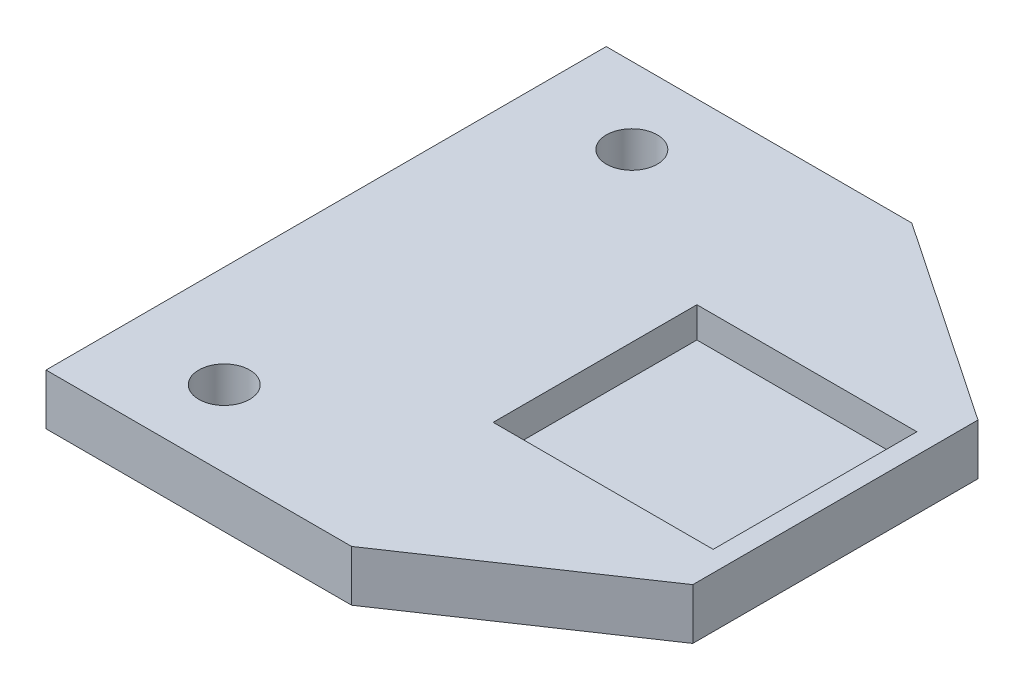
SolidWorks part; units mm, degrees
ref_plane "Front Plane" through (0, 0, 0) normal (0, 0, 1) x (1, 0, 0)
ref_plane "Top Plane" through (0, 0, 0) normal (0, 1, 0) x (1, 0, 0)
ref_plane "Right Plane" through (0, 0, 0) normal (1, 0, 0) x (0, 0, -1)
sketch "Sketch1" plane through (0, 0, 0) normal (0, 1, 0) x (1, 0, 0)
  line L0 (50.8, 7.62) -> (25.4, -9.525)
  line L1 (0, 0) -> (25.4, 0) construction
  line L2 (0, 0) -> (0, 50.8) construction
  line L3 (0, 50.8) -> (25.4, 50.8) construction
  line L4 (25.4, 0) -> (25.4, 50.8) construction
  line L5 (-12.7, 60.325) -> (25.4, 60.325)
  line L6 (-12.7, 60.325) -> (-12.7, -9.525)
  line L7 (-12.7, -9.525) -> (25.4, -9.525)
  line L8 (25.4, 60.325) -> (25.4, -9.525)
  line L9 (25.4, 43.18) -> (50.8, 43.18)
  line L10 (25.4, 43.18) -> (25.4, 7.62)
  line L11 (25.4, 7.62) -> (50.8, 7.62)
  line L12 (50.8, 43.18) -> (50.8, 7.62)
  line L13 (50.8, 43.18) -> (25.4, 60.325)
  circle A0 centre (0, 0) radius 3.175
  circle A1 centre (0.0159, 50.8047) radius 3.175
  dimension "D1" = 6.35
  dimension "D3" = 6.35
  dimension "D2" = 50.8
  dimension "D4" = 25.4
  dimension "D5" = 69.85
  dimension "D6" = 9.525
  dimension "D7" = 38.1
  dimension "D8" = 25.4
  dimension "D9" = 35.56
  dimension "D10" = 17.145
extrude "Boss-Extrude1" add sketch "Sketch1" along normal blind 6.35 contours L8 L5 L6 L7 A1 A0 | L9 L13 L8 | L12 L9 L8 L11 | L11 L8 L0 region at (33.8667, 0, -1.905) region at (38.1, 0, -25.4) region at (6.5046, 0, -25.3999) region at (33.8667, 0, -48.895)
sketch "Sketch2" plane through (0, 6.35, 0) normal (0, 1, 0) x (1, 0, 0)
  line L0 (50.8, 43.18) -> (50.8, 7.62) construction
  line L5 (25.4, 60.325) -> (25.4, -9.525) construction
  line L6 (50.8, 43.18) -> (-12.7, 43.18) construction
  line L7 (-12.7, 60.325) -> (-12.7, -9.525) construction
  line L8 (50.8, 7.62) -> (-12.7, 7.62) construction
  line L9 (20.828, 38.1) -> (48.26, 38.1)
  line L14 (20.828, 38.1) -> (20.828, 12.7)
  line L15 (20.828, 12.7) -> (48.26, 12.7)
  line L16 (48.26, 38.1) -> (48.26, 12.7)
  dimension "D1" = 27.432
  dimension "D2" = 25.4
  dimension "D3" = 5.08
  dimension "D4" = 2.54
extrude "Cut-Extrude1" cut sketch "Sketch2" against normal blind 3.81
